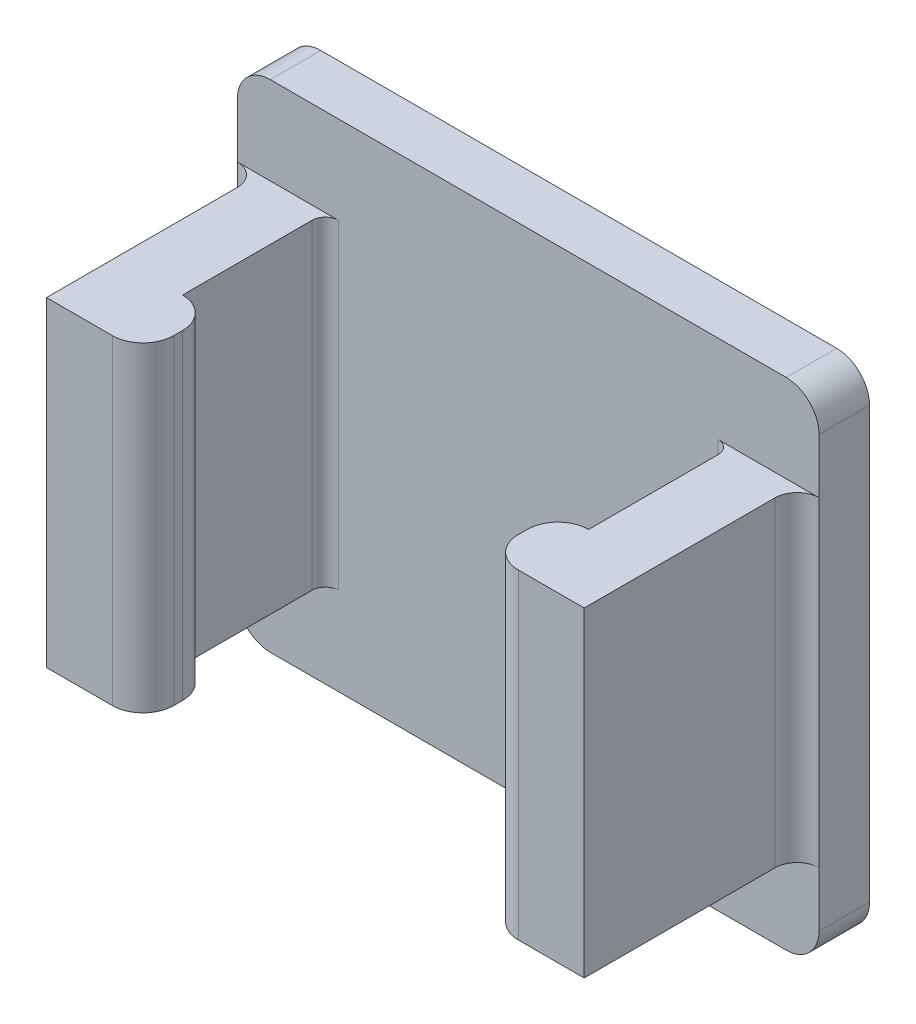
SolidWorks part; units mm, degrees
ref_plane "정면" through (0, 0, 0) normal (0, 0, 1) x (1, 0, 0)
ref_plane "윗면" through (0, 0, 0) normal (0, 1, 0) x (1, 0, 0)
ref_plane "우측면" through (0, 0, 0) normal (1, 0, 0) x (0, 0, -1)
sketch "스케치1" plane through (0, 0, 0) normal (0, 0, 1) x (1, 0, 0)
  line L1 (-6.125, -5.65) -> (6.125, -5.65)
  line L2 (-6.125, -5.65) -> (-6.125, 5.65)
  line L3 (-6.125, 5.65) -> (6.125, 5.65)
  line L4 (6.125, -5.65) -> (6.125, 5.65)
  line L5 (-6.125, -5.65) -> (6.125, 5.65) construction
  line L6 (-6.125, 5.65) -> (6.125, -5.65) construction
  point P0 (0, 0)
  dimension "D1" = 12.25
  dimension "D2" = 11.3
extrude "보스-돌출1" add sketch "스케치1" along normal blind 2.15
sketch "스케치2" plane through (0, 0, 2.15) normal (0, 0, 1) x (1, 0, 0)
  line L0 (-6.125, -5.65) -> (6.125, -5.65) construction
  line L1 (-6.125, 5.65) -> (-4.625, 5.65)
  line L2 (-6.125, 5.65) -> (-6.125, -5.65)
  line L3 (-6.125, -5.65) -> (-4.625, -5.65)
  line L4 (-4.625, 5.65) -> (-4.625, -5.65)
  line L6 (6.125, 5.65) -> (4.625, 5.65)
  line L7 (6.125, 5.65) -> (6.125, -5.65)
  line L8 (6.125, -5.65) -> (4.625, -5.65)
  line L9 (4.625, 5.65) -> (4.625, -5.65)
  dimension "D1" = 1.5
  dimension "D2" = 1.5
extrude "보스-돌출2" add sketch "스케치2" along normal blind 3.85
sketch "스케치5" plane through (0, 0, 2.15) normal (0, 0, 1) x (1, 0, 0)
  line L0 (4.625, 5.65) -> (4.625, -5.65) construction
  line L1 (-4.625, -5.75) -> (4.625, -5.75)
  line L2 (-4.625, -5.75) -> (-4.625, 5.75)
  line L3 (-4.625, 5.75) -> (4.625, 5.75)
  line L4 (4.625, -5.75) -> (4.625, 5.75)
  line L5 (-4.625, -5.75) -> (4.625, 5.75) construction
  line L6 (-4.625, 5.75) -> (4.625, -5.75) construction
  point P0 (0, 0)
  dimension "D1" = 11.5
extrude "컷-돌출1" cut sketch "스케치5" against normal blind 1
sketch "스케치8" plane through (-4.625, 0, 0) normal (1, 0, 0) x (0, 0, -1)
  line L0 (-6, -5.65) -> (-1.15, -5.65) construction
  line L1 (-6, 5.65) -> (-4.4, 5.65)
  line L2 (-6, 5.65) -> (-6, -5.65)
  line L3 (-6, -5.65) -> (-4.4, -5.65)
  line L4 (-4.4, 5.65) -> (-4.4, -5.65)
  dimension "D1" = 1.6
extrude "보스-돌출5" add sketch "스케치8" along normal blind 0.7
sketch "스케치9" plane through (4.625, 0, 0) normal (-1, 0, 0) x (0, 0, 1)
  line L0 (6, 5.65) -> (1.15, 5.65) construction
  line L1 (6, -5.65) -> (4.4, -5.65)
  line L2 (6, -5.65) -> (6, 5.65)
  line L3 (6, 5.65) -> (4.4, 5.65)
  line L4 (4.4, -5.65) -> (4.4, 5.65)
  dimension "D1" = 1.6
extrude "보스-돌출6" add sketch "스케치9" along normal blind 0.7
fillet "필렛8" radius 0.3 2 edges at (4.625, 0, 1.15) (-4.625, 0, 1.15)
sketch "스케치11" plane through (0, 5.65, 0) normal (0, 1, 0) x (1, 0, 0)
  line L0 (6.125, -6) -> (6.125, 0) construction
  line L1 (-6.125, -6) -> (6.125, -6)
  line L2 (-6.125, -6) -> (-6.125, -1.15)
  line L3 (-6.125, -1.15) -> (6.125, -1.15)
  line L4 (6.125, -6) -> (6.125, -1.15)
  line L5 (-4.325, -1.15) -> (4.325, -1.15) construction
  dimension "D1" = 0
extrude "컷-돌출2" cut sketch "스케치11" against normal blind 2
sketch "스케치12" plane through (0, -5.65, 0) normal (0, -1, 0) x (1, 0, 0)
  line L0 (6.125, 6) -> (6.125, 0) construction
  line L1 (-6.125, 6) -> (6.125, 6)
  line L2 (-6.125, 6) -> (-6.125, 1.15)
  line L3 (-6.125, 1.15) -> (6.125, 1.15)
  line L4 (6.125, 6) -> (6.125, 1.15)
  line L5 (4.325, 1.15) -> (-4.325, 1.15) construction
  dimension "D1" = 0
extrude "컷-돌출3" cut sketch "스케치12" against normal blind 2
sketch "스케치13" plane through (6.125, 0, 0) normal (1, 0, 0) x (0, 0, -1)
  line L1 (-1.15, 5.65) -> (0, 5.65)
  line L2 (-1.15, 5.65) -> (-1.15, -5.65)
  line L3 (-1.15, -5.65) -> (0, -5.65)
  line L4 (0, 5.65) -> (0, -5.65)
extrude "보스-돌출7" add sketch "스케치13" along normal blind 0.5
sketch "스케치14" plane through (-6.125, 0, 0) normal (-1, 0, 0) x (0, 0, 1)
  line L1 (1.15, 5.65) -> (0, 5.65)
  line L2 (1.15, 5.65) -> (1.15, -5.65)
  line L3 (1.15, -5.65) -> (0, -5.65)
  line L4 (0, 5.65) -> (0, -5.65)
extrude "보스-돌출8" add sketch "스케치14" along normal blind 0.5
fillet "필렛9" radius 0.5 2 edges at (6.125, 0, 1.15) (-6.125, 0, 1.15)
fillet "필렛10" radius 0.7 4 edges at (-3.925, 0, 6) (-3.925, 0, 4.4) (3.925, 0, 4.4) (3.925, 0, 6)
fillet "필렛11" radius 0.75 4 edges at (6.625, -5.65, 0.575) (-6.625, -5.65, 0.575) (-6.625, 5.65, 0.575) (6.625, 5.65, 0.575)
